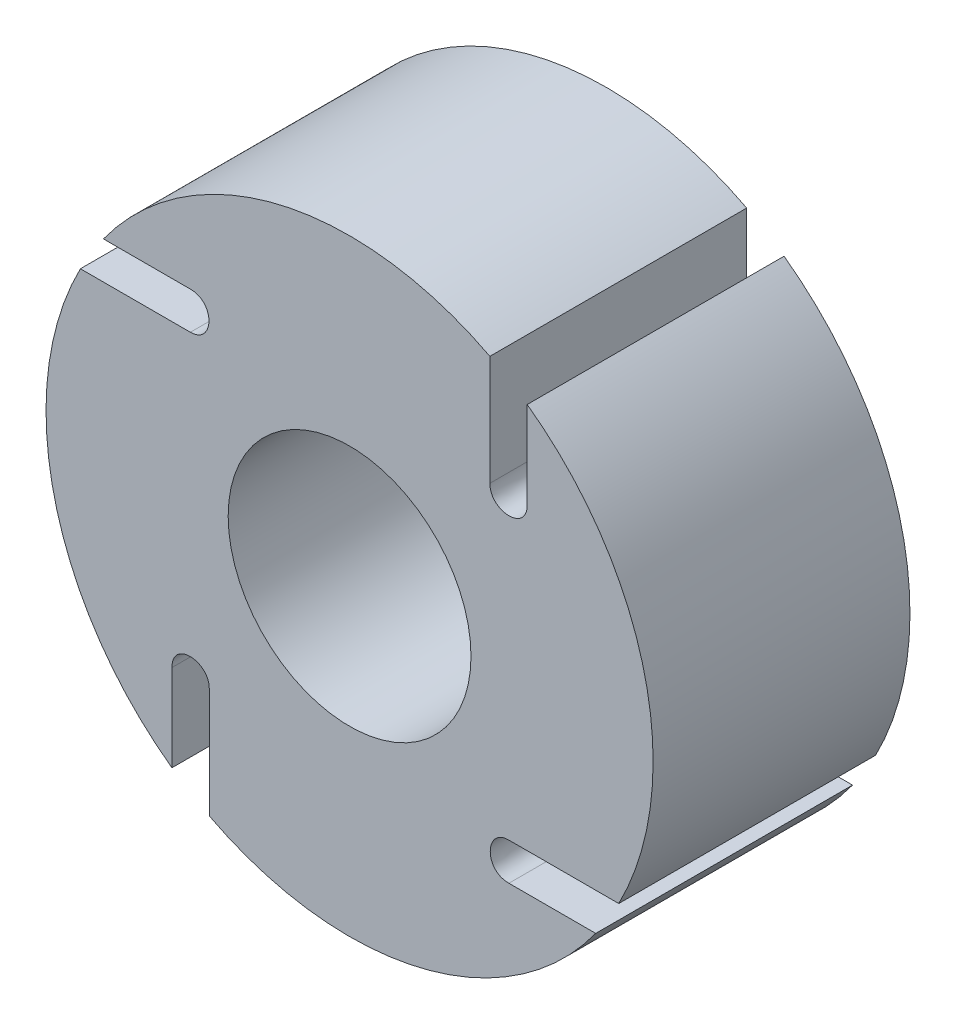
SolidWorks part; units mm, degrees
ref_plane "Front Plane" through (0, 0, 0) normal (0, 0, 1) x (1, 0, 0)
ref_plane "Top Plane" through (0, 0, 0) normal (0, 1, 0) x (1, 0, 0)
ref_plane "Right Plane" through (0, 0, 0) normal (1, 0, 0) x (0, 0, -1)
sketch "Sketch2" plane through (0, 0, 0) normal (0, 0, 1) x (1, 0, 0)
  circle A0 centre (7.1655, 7.312) radius 6.5
  dimension "D1" = 13
sketch "Sketch1" plane through (0, 0, 0) normal (0, 0, 1) x (1, 0, 0)
  line L0 (10.9696, 10.7238) -> (10.9696, 13.0117)
  line L1 (10.1696, 13.2155) -> (10.1696, 10.7211)
  line L2 (10.9696, 11.8647) -> (10.9696, 10.9801) construction
  line L3 (10.1696, 10.9263) -> (10.1696, 11.9133) construction
  line L4 (13.0691, 4.3079) -> (10.5747, 4.3079)
  line L5 (10.5773, 3.5079) -> (12.8653, 3.5079)
  line L6 (4.1615, 1.4084) -> (4.1615, 3.9028)
  line L7 (3.3615, 3.9002) -> (3.3615, 1.6122)
  line L8 (1.262, 10.316) -> (3.7564, 10.316)
  line L9 (3.7537, 11.116) -> (1.4658, 11.116)
  circle A0 centre (7.1655, 7.312) radius 2.6
  circle A1 centre (7.1655, 7.312) radius 5 construction
  arc A2 (10.1149, 14.2077) -> (10.9696, 13.7757) centre (7.1655, 7.312) ccw construction
  spline S0 degree 3 poles (10.1696, 10.7211) (10.1696, 10.2119) (10.9696, 10.1709) (10.9696, 10.7238) knots 0 0 0 0 1 1 1 1
  spline S1 degree 3 poles (10.9696, 13.0117) (10.9586, 13.4756) (10.1623, 13.5091) (10.1696, 13.2155) knots 0 0 0 0 1 1 1 1
  spline S2 degree 3 poles (12.8653, 3.5079) (13.3292, 3.5189) (13.3627, 4.3152) (13.0691, 4.3079) knots 0 0 0 0 1 1 1 1
  spline S3 degree 3 poles (10.5747, 4.3079) (10.0655, 4.3079) (10.0244, 3.5079) (10.5773, 3.5079) knots 0 0 0 0 1 1 1 1
  spline S4 degree 3 poles (3.3615, 1.6122) (3.3724, 1.1483) (4.1688, 1.1148) (4.1615, 1.4084) knots 0 0 0 0 1 1 1 1
  spline S5 degree 3 poles (4.1615, 3.9028) (4.1615, 4.412) (3.3615, 4.4531) (3.3615, 3.9002) knots 0 0 0 0 1 1 1 1
  spline S6 degree 3 poles (1.4658, 11.116) (1.0019, 11.1051) (0.9684, 10.3087) (1.262, 10.316) knots 0 0 0 0 1 1 1 1
  spline S7 degree 3 poles (3.7564, 10.316) (4.2656, 10.316) (4.3066, 11.116) (3.7537, 11.116) knots 0 0 0 0 1 1 1 1
  point P23 (7.1655, 7.312)
  point P28 (7.1655, 7.312)
  point P30 (7.1655, 7.312)
  point P36 (7.1655, 7.312)
  dimension "D1" = 5.2
  dimension "D2" = 10
  dimension "D3" = 15
  dimension "D5" = 4
  dimension "D4" = 0.8
extrude "Boss-Extrude2" add sketch "Sketch2" against normal blind 5.5
extrude "Cut-Extrude1" cut sketch "Sketch1" against normal through all
ref_axis "Axis1" through (7.1655, 7.312, -5.5) along (0, 0, 1)
